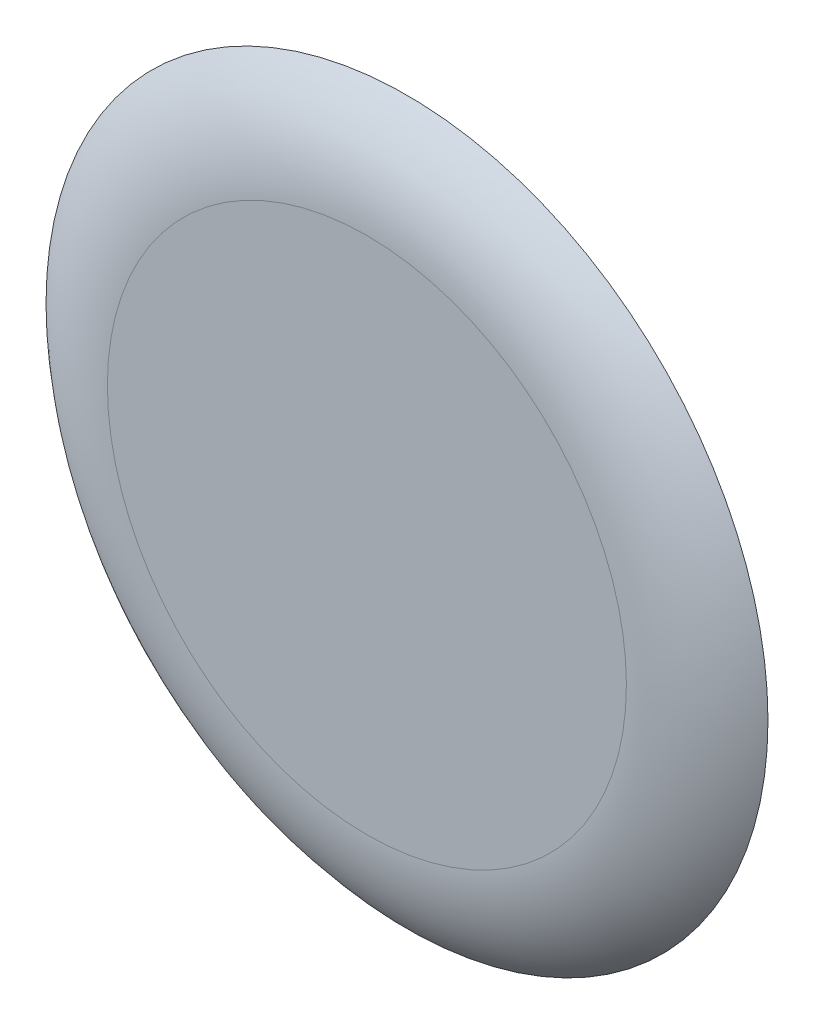
SolidWorks part; units mm, degrees
ref_plane "Front Plane" through (0, 0, 0) normal (0, 0, 1) x (1, 0, 0)
ref_plane "Top Plane" through (0, 0, 0) normal (0, 1, 0) x (1, 0, 0)
ref_plane "Right Plane" through (0, 0, 0) normal (1, 0, 0) x (0, 0, -1)
sketch "Sketch1" plane through (0, 0, 0) normal (0, 0, 1) x (1, 0, 0)
  circle A0 centre (0, 0) radius 4.5
  dimension "D1" = 9
extrude "Boss-Extrude1" add sketch "Sketch1" along normal blind 0.5
fillet "Fillet2" radius 1.85 1 edges at (4.5, 0, 0.5)
